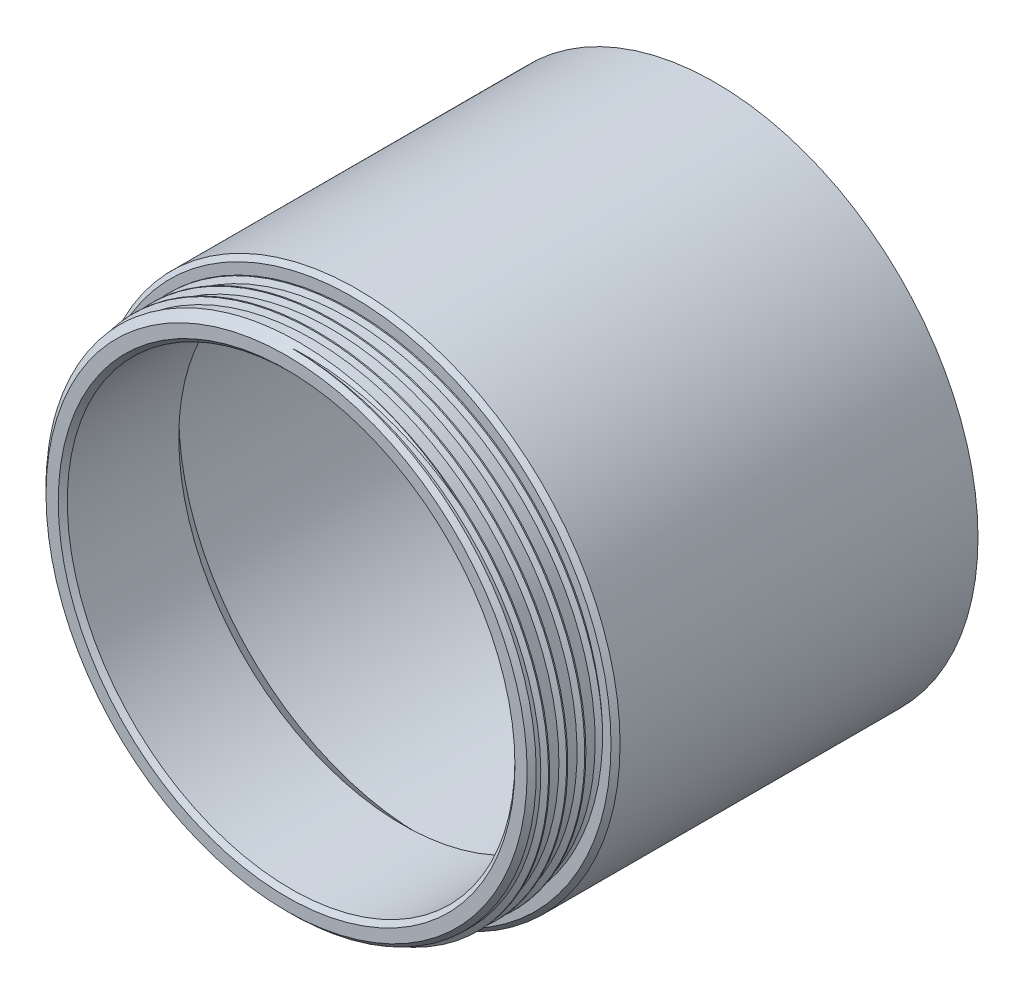
SolidWorks part; units mm, degrees
ref_plane "Front Plane" through (0, 0, 0) normal (0, 0, 1) x (1, 0, 0)
ref_plane "Top Plane" through (0, 0, 0) normal (0, 1, 0) x (1, 0, 0)
ref_plane "Right Plane" through (0, 0, 0) normal (1, 0, 0) x (0, 0, -1)
sketch "Sketch1" plane through (0, 0, 0) normal (0, 0, 1) x (1, 0, 0)
  circle A0 centre (0, 0) radius 29
  circle A1 centre (0, 0) radius 26.9
  dimension "D1" = 53.8
  dimension "D2" = 58
extrude "Extrude1" add sketch "Sketch1" along normal blind 40
sketch "Sketch2" plane through (0, 0, 40) normal (0, 0, 1) x (1, 0, 0)
  circle A0 centre (0, 0) radius 27.05
  circle A1 centre (0, 0) radius 24.7
  dimension "D1" = 49.4
  dimension "54,6" = 54.1
extrude "Extrude2" add sketch "Sketch2" along normal blind 7.3 and the other way blind 8
thread "Thread1" pitch 1 method extrude trim with start face yes trim with end face yes profile "Sketch4" start angle 0, offset 2, length 0, pitch 2, diameter 54.1
ref_plane "Plane1" through (-27.05, 0, 49.3) normal (0, -1, 0) x (-1, 0, 0)
sketch "Sketch4" plane through (-27.05, 0, 49.3) normal (0, -1, 0) x (-1, 0, 0)
  line L0 (0, 0) -> (0, 1) construction
  line L1 (0, 0) -> (0.5413, 0.3125)
  line L2 (0.5413, 0.3125) -> (0.5413, 0.4375)
  line L3 (0.5413, 0.4375) -> (0, 0.75)
  line L4 (0.5413, 0.375) -> (0, 0.375) construction
  line L11 (0, 0) -> (0, 0.75)
  point P2 (0, 0)
  dimension "Pitch" = 1
  dimension "Profile_Angle" = 60
  dimension "Profile_Land" = 0.125
  dimension "Profile_Height" = 0.5413
chamfer "Chamfer1" distance 0.5 angle 45 2 edges at (24.7, 0, 47.3) (29, 0, 40)
chamfer "Chamfer2" distance 2.5 angle 45 1 edges at (24.7, 0, 32)
sketch "Sketch7" plane through (0, 0, 0) normal (0, 1, 0) x (1, 0, 0)
  line L0 (-28.009, -45.841) -> (-26.55, -47.3)
  line L1 (-27.05, -47.3) -> (27.05, -47.3) construction
  line L2 (-26.55, -47.3) -> (-27.05, -47.3)
  line L3 (-27.05, -47.3) -> (-28.6806, -47.3)
  line L4 (-28.6806, -47.3) -> (-28.6806, -45.841)
  line L5 (-28.6806, -45.841) -> (-28.009, -45.841)
  line L7 (0, 0) -> (0, -56.4023) construction
  dimension "D1" = 45
  dimension "D2" = 0.5
revolve "Cut-Revolve1" cut sketch "Sketch7" angle 360 about L7
chamfer "Chamfer4" distance 0.25 angle 45 1 edges at (26.9, 0, 0)
sketch "Sketch6" plane through (0, 0, 0) normal (0, 0, -1) x (-1, 0, 0)
  circle A0 centre (0, 0) radius 34.2486
extrude "Cut-Extrude1" [suppressed] cut sketch "Sketch6" against normal blind 36
chamfer "Chamfer3" [suppressed] distance 0.2 angle 45
